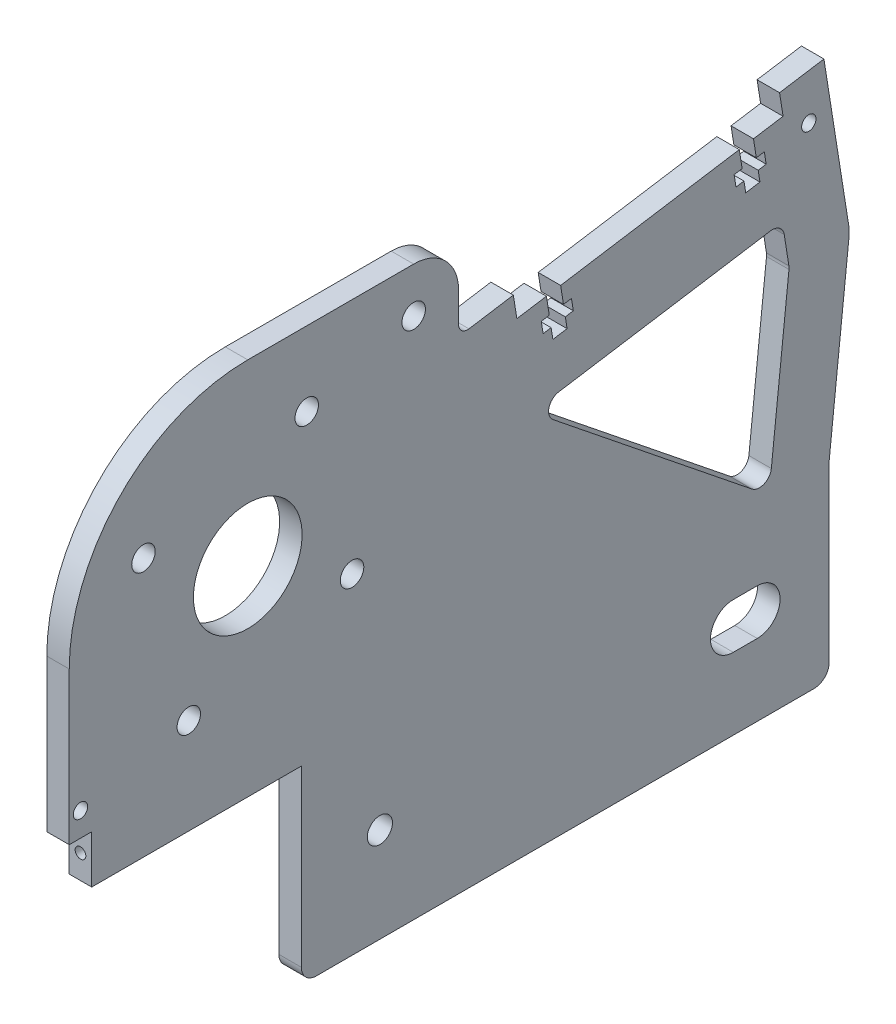
SolidWorks part; units mm, degrees
ref_plane "Front Plane" through (0, 0, 0) normal (0, 0, 1) x (1, 0, 0)
ref_plane "Top Plane" through (0, 0, 0) normal (0, 1, 0) x (1, 0, 0)
ref_plane "Right Plane" through (0, 0, 0) normal (1, 0, 0) x (0, 0, -1)
sketch "Sketch1" plane through (0, 0, 0) normal (1, 0, 0) x (0, 0, -1)
  line L0 (-28.1703, 0) -> (77.3828, 0)
  line L1 (80.5578, 3.175) -> (80.5578, 40.132)
  line L2 (-80.5578, 82.55) -> (-80.5578, 50.292)
  line L3 (4.1952, 102.6435) -> (13.6029, 104.1335)
  line L4 (-75.7953, 50.292) -> (-75.7953, 40.132)
  line L5 (-80.5578, 50.292) -> (-75.7953, 50.292)
  line L6 (65.3178, 20.066) -> (60.2378, 20.066) construction
  line L7 (-75.7953, 40.132) -> (-31.3453, 40.132)
  line L8 (1.9922, 110.875) -> (1.9922, 104.525)
  line L9 (-42.7078, 120.4) -> (-7.5328, 120.4)
  line L10 (-31.3453, 40.132) -> (-31.3453, 3.175)
  line L11 (-37.7935, 96.5728) -> (77.9184, 56.022) construction
  line L12 (-52.4128, 71.2982) -> (40.4331, -8.7847) construction
  line L13 (65.3178, 15.2273) -> (60.2378, 15.2273)
  line L14 (65.3178, 24.9047) -> (60.2378, 24.9047)
  line L15 (4.1952, 102.6435) -> (101.0919, 102.6435) construction
  line L16 (13.6029, 104.1335) -> (14.348, 99.4297)
  line L17 (14.348, 99.4297) -> (20.6198, 100.423)
  line L18 (70.7944, 108.3699) -> (70.0493, 113.0738)
  line L19 (70.0493, 113.0738) -> (79.4571, 114.5638)
  line L20 (79.4571, 114.5638) -> (84.7184, 81.3449)
  line L21 (84.7717, 79.1961) -> (80.5578, 40.132)
  line L22 (20.6198, 100.423) -> (21.2208, 96.6286)
  line L23 (21.2208, 96.6286) -> (19.5274, 96.3604)
  line L24 (19.5274, 96.3604) -> (19.9198, 93.883)
  line L25 (19.9198, 93.883) -> (21.6131, 94.1512)
  line L26 (26.317, 94.8962) -> (25.9246, 97.3736)
  line L27 (25.9246, 97.3736) -> (24.2312, 97.1054)
  line L28 (24.2312, 97.1054) -> (23.6303, 100.8998)
  line L29 (23.6303, 100.8998) -> (61.5121, 106.8997)
  line L30 (64.5225, 107.3765) -> (70.7944, 108.3699)
  line L31 (71.0359, 86.549) -> (72.0272, 80.29)
  line L38 (21.6131, 94.1512) -> (21.9857, 91.7993)
  line L39 (21.9857, 91.7993) -> (24.9961, 92.2761)
  line L40 (24.9961, 92.2761) -> (24.6236, 94.628)
  line L41 (24.6236, 94.628) -> (26.317, 94.8962)
  line L46 (61.5121, 106.8997) -> (62.113, 103.1053)
  line L47 (68.1298, 88.6604) -> (23.2189, 81.5472)
  line L48 (22.0267, 77.0573) -> (64.1879, 43.2308)
  line L49 (68.3027, 44.9396) -> (72.0438, 79.6202)
  line L50 (62.113, 103.1053) -> (60.4196, 102.8371)
  line L51 (60.4196, 102.8371) -> (60.812, 100.3597)
  line L52 (60.812, 100.3597) -> (62.5054, 100.6279)
  line L53 (67.2093, 101.3729) -> (66.8169, 103.8503)
  line L54 (66.8169, 103.8503) -> (65.1235, 103.5821)
  line L55 (65.1235, 103.5821) -> (64.5225, 107.3765)
  line L56 (62.5054, 100.6279) -> (62.8779, 98.276)
  line L57 (62.8779, 98.276) -> (65.8884, 98.7528)
  line L58 (65.8884, 98.7528) -> (65.5159, 101.1047)
  line L59 (65.5159, 101.1047) -> (67.2093, 101.3729)
  arc A0 (65.3178, 15.2273) -> (65.3178, 24.9047) centre (65.3178, 20.066) ccw
  circle A1 centre (-42.7078, 82.55) radius 31.5 construction
  circle A2 centre (65.3178, 20.066) radius 78.105 construction
  circle A3 centre (65.3178, 20.066) radius 38.1 construction
  circle A4 centre (-42.7078, 82.55) radius 14.859 construction
  arc A5 (-42.7078, 120.4) -> (-80.5578, 82.55) centre (-42.7078, 82.55) ccw
  arc A6 (-28.1703, 0) -> (-31.3453, 3.175) centre (-28.1703, 3.175) cw
  arc A7 (77.3828, 0) -> (80.5578, 3.175) centre (77.3828, 3.175) ccw
  circle A9 centre (-7.5328, 110.875) radius 6.35 construction
  circle A10 centre (-55.209, 60.4394) radius 2.4892
  circle A11 centre (-14.6922, 20.066) radius 2.667
  circle A12 centre (-20.5972, 70.0488) radius 2.4892
  circle A13 centre (-64.8184, 95.0512) radius 2.4892
  circle A14 centre (-30.2065, 104.6606) radius 2.4892
  circle A15 centre (-78.1765, 55.372) radius 1.524
  circle A16 centre (-42.7078, 82.55) radius 11.5228
  arc A17 (60.2378, 24.9047) -> (60.2378, 15.2273) centre (60.2378, 20.066) ccw
  arc A18 (-7.5328, 120.4) -> (1.9922, 110.875) centre (-7.5328, 110.875) cw
  circle A19 centre (-7.5328, 110.875) radius 2.4892
  arc A20 (4.1952, 102.6435) -> (1.9922, 104.525) centre (3.8972, 104.525) cw
  arc A21 (84.7184, 81.3449) -> (84.7717, 79.1961) centre (76.6695, 80.0701) cw
  circle A22 centre (76.2432, 104.411) radius 1.524
  arc A23 (72.0438, 79.6202) -> (72.0272, 80.29) centre (69.5185, 79.8927) ccw
  arc A24 (64.1879, 43.2308) -> (68.3027, 44.9396) centre (65.7774, 45.212) ccw
  arc A25 (23.2189, 81.5472) -> (22.0267, 77.0573) centre (23.6162, 79.0385) ccw
  arc A26 (68.1298, 88.6604) -> (71.0359, 86.549) centre (68.5271, 86.1517) cw
  point P39 (62.7778, 20.066)
  dimension "D4" = 9.6774
  dimension "D7" = 29.718
  dimension "D8" = 63
  dimension "D9" = 6.35
  dimension "D12" = 3.175
  dimension "D13" = 4.7625
  dimension "D14" = 76.2
  dimension "D15" = 156.21
  dimension "D18" = 5.334
  dimension "D19" = 9.525
  dimension "D20" = 9.525
  dimension "D23" = 3.048
  dimension "D27" = 73.025
  dimension "D28" = 12.7
  dimension "D29" = 4.9784
  dimension "D31" = 1.905
  dimension "D33" = 3.048
  dimension "D42" = 2.54
  dimension "D43" = 2.54
  dimension "D44" = 86.36
  dimension "D48" = 3.048
  dimension "D49" = 9.525
  dimension "D2" = 40.132
  dimension "D3" = 20.066
  dimension "D5" = 15.24
  dimension "D6" = 44.45
  dimension "D10" = 161.1156
  dimension "D11" = 95.25
  dimension "D17" = 9
  dimension "D21" = 4.7625
  dimension "D22" = 10.16
  dimension "D24" = 5.08
  dimension "D25" = 2.3813
  dimension "D26" = 5.08
  dimension "D16" = 76.2
  dimension "D30" = 9.525
  dimension "D34" = 19.05
  dimension "D35" = 8.7312
  dimension "D36" = 2.5083
  dimension "D37" = 6.477
  dimension "D38" = 6.35
  dimension "D40" = 12.7
  dimension "D45" = 6.35
  dimension "D46" = 6.35
  dimension "D47" = 4.7625
  dimension "D50" = 5.08
  dimension "D39" = 2
extrude "Boss-Extrude1" add sketch "Sketch1" along normal blind 4.7625
sketch "Sketch2" plane through (0, 0, 75.7953) normal (0, 0, 1) x (1, 0, 0)
  line L0 (4.7625, 50.292) -> (4.7625, 40.132) construction
  line L1 (4.7625, 40.132) -> (0, 40.132) construction
  circle A0 centre (2.3813, 45.212) radius 1.1303
  point P4 (4.7625, 45.212)
  point P7 (2.3813, 40.132)
  dimension "D1" = 2.2606
extrude "Cut-Extrude1" cut sketch "Sketch2" against normal blind 6.35
